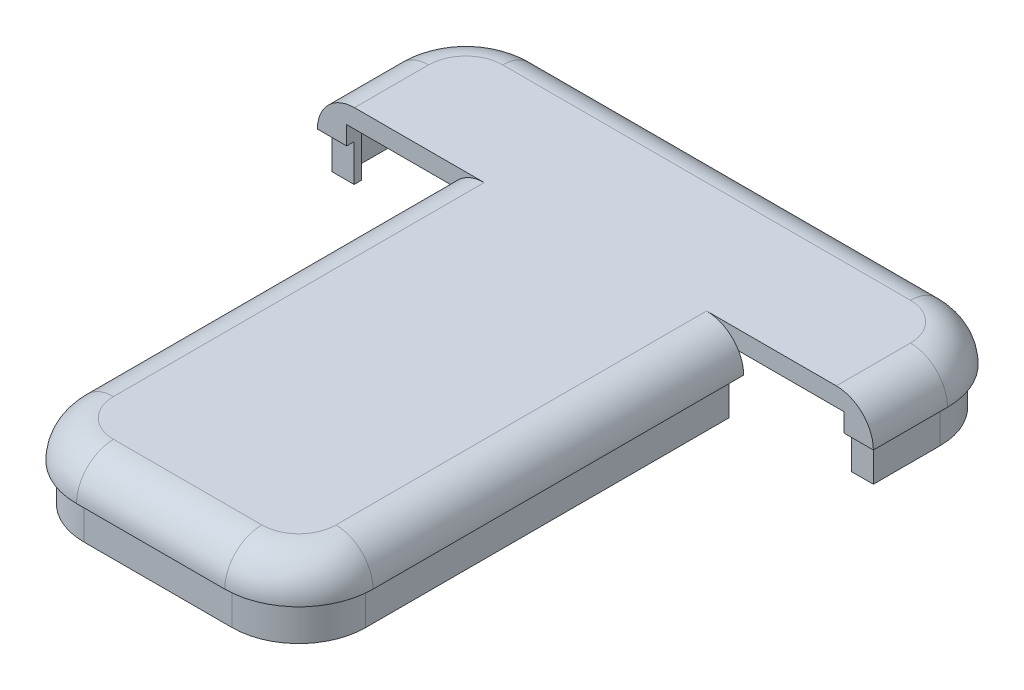
SolidWorks part; units mm, degrees
ref_plane "Front Plane" through (0, 0, 0) normal (0, 0, 1) x (1, 0, 0)
ref_plane "Top Plane" through (0, 0, 0) normal (0, 1, 0) x (1, 0, 0)
ref_plane "Right Plane" through (0, 0, 0) normal (1, 0, 0) x (0, 0, -1)
sketch "Sketch1" plane through (0, 0, 0) normal (0, 1, 0) x (1, 0, 0)
  line L0 (0, 0) -> (0, 152.4)
  line L1 (0, 152.4) -> (-44.45, 152.4)
  line L2 (-44.45, 152.4) -> (-44.45, 203.2)
  line L3 (-44.45, 203.2) -> (146.05, 203.2)
  line L4 (0, 0) -> (101.6, 0)
  line L5 (50.8, 203.2) -> (50.8, 0) construction
  line L6 (101.6, 0) -> (101.6, 152.4)
  line L7 (101.6, 152.4) -> (146.05, 152.4)
  line L8 (146.05, 152.4) -> (146.05, 203.2)
  dimension "D2" = 152.4
  dimension "D3" = 50.8
  dimension "D4" = 44.45
  dimension "D5" = 95.25
extrude "Boss-Extrude1" add sketch "Sketch1" along normal blind 12.7
fillet "Fillet5" radius 25.4 4 edges at (-44.45, 6.35, -203.2) (0, 6.35, 0) (101.6, 6.35, 0) (146.05, 6.35, -203.2)
fillet "Fillet6" radius 12.7 10 edges at (94.1605, 12.7, -7.4395) (50.8, 12.7, 0) (7.4395, 12.7, -7.4395) (0, 12.7, -88.9) (101.6, 12.7, -88.9) (146.05, 12.7, -165.1) (138.6105, 12.7, -195.7605) (-44.45, 12.7, -165.1) (-37.0105, 12.7, -195.7605) (50.8, 12.7, -203.2)
shell "Shell1" thickness 2.54 removed face at (50.8, 0, -118.5333)
ref_plane "Plane2" through (0, 0, 0) normal (0, 1, 0) x (1, 0, 0)
sketch "Sketch3" plane through (0, 0, 0) normal (0, 1, 0) x (1, 0, 0)
  line L16 (96.52, 157.48) -> (140.97, 157.48)
  line L17 (140.97, 157.48) -> (140.97, 177.8)
  line L18 (120.65, 198.12) -> (-19.05, 198.12)
  line L19 (-39.37, 177.8) -> (-39.37, 157.48)
  line L20 (-39.37, 157.48) -> (5.08, 157.48)
  line L21 (5.08, 157.48) -> (5.08, 25.4)
  line L22 (25.4, 5.08) -> (76.2, 5.08)
  line L23 (96.52, 25.4) -> (96.52, 157.48)
  line L24 (96.52, 157.48) -> (140.97, 157.48)
  line L25 (140.97, 157.48) -> (140.97, 177.8)
  line L26 (120.65, 198.12) -> (-19.05, 198.12)
  line L27 (-39.37, 177.8) -> (-39.37, 157.48)
  line L28 (-39.37, 157.48) -> (5.08, 157.48)
  line L29 (5.08, 157.48) -> (5.08, 25.4)
  line L30 (25.4, 5.08) -> (76.2, 5.08)
  line L31 (96.52, 25.4) -> (96.52, 157.48)
  arc A8 (140.97, 177.8) -> (120.65, 198.12) centre (120.65, 177.8) ccw
  arc A9 (-19.05, 198.12) -> (-39.37, 177.8) centre (-19.05, 177.8) ccw
  arc A10 (5.08, 25.4) -> (25.4, 5.08) centre (25.4, 25.4) ccw
  arc A11 (76.2, 5.08) -> (96.52, 25.4) centre (76.2, 25.4) ccw
  arc A12 (140.97, 177.8) -> (120.65, 198.12) centre (120.65, 177.8) ccw
  arc A13 (-19.05, 198.12) -> (-39.37, 177.8) centre (-19.05, 177.8) ccw
  arc A14 (5.08, 25.4) -> (25.4, 5.08) centre (25.4, 25.4) ccw
  arc A15 (76.2, 5.08) -> (96.52, 25.4) centre (76.2, 25.4) ccw
  dimension "D1" = 2.54
extrude "Extrude-Thin1" add sketch "Sketch3" along normal up to next thin thin type one direction wall 2.54
extrude "Extrude-Thin2" add sketch "Sketch3<2>" against normal blind 12.7 thin thin type one direction wall 2.54
sketch "Sketch3<2>" plane through (0, 0, 0) normal (0, 1, 0) x (1, 0, 0) same geometry as "Sketch3"
sketch "Sketch4" plane through (0, 0, 0) normal (0, 1, 0) x (1, 0, 0)
  line L0 (0, 152.4) -> (5.08, 152.4) construction
  line L1 (101.6, 152.4) -> (96.52, 152.4) construction
  line L2 (96.52, 152.4) -> (5.08, 152.4)
extrude "Extrude-Thin3" add sketch "Sketch4" along normal up to next thin thin type one direction reverse wall 2.54
sketch "Sketch5" plane through (0, 0, -149.86) normal (0, 0, 1) x (1, 0, 0)
  line L0 (96.52, 0) -> (5.08, 0) construction
  line L1 (46.99, 0) -> (54.61, 0)
  arc A0 (54.61, 0) -> (46.99, 0) centre (50.8, 0) ccw
extrude "Cut-Extrude1" cut sketch "Sketch5" against normal up to next
sketch "Sketch6" plane through (0, -12.7, 0) normal (0, -1, 0) x (1, 0, 0)
  line L0 (50.8, -5.08) -> (50.8, -200.66) construction
  line L1 (25.4, -5.08) -> (76.2, -5.08) construction
  line L2 (120.65, -200.66) -> (-19.05, -200.66) construction
  line L3 (96.52, -154.94) -> (136.017, -154.94)
  line L4 (99.06, -154.94) -> (143.51, -154.94) construction
  line L7 (96.52, -157.48) -> (96.52, -154.94)
  line L10 (5.08, -154.94) -> (-34.417, -154.94)
  line L11 (5.08, -157.48) -> (5.08, -154.94)
  line L12 (2.54, -154.94) -> (2.54, -149.86)
  line L13 (2.54, -154.94) -> (2.54, -25.4) construction
  line L14 (2.54, -149.86) -> (5.08, -149.86)
  line L15 (5.08, -157.48) -> (5.08, -25.4) construction
  line L16 (5.08, -149.86) -> (5.08, -154.94)
  line L17 (2.54, -154.94) -> (5.08, -154.94)
  line L18 (99.06, -154.94) -> (96.52, -154.94)
  line L19 (99.06, -154.94) -> (99.06, -149.86)
  line L20 (99.06, -149.86) -> (96.52, -149.86)
  line L21 (96.52, -149.86) -> (96.52, -154.94)
  line L22 (96.52, -157.48) -> (136.017, -157.48)
  line L23 (96.52, -157.48) -> (140.97, -157.48) construction
  line L24 (136.017, -157.48) -> (136.017, -154.94)
  line L25 (-34.417, -154.94) -> (-34.417, -157.48)
  line L26 (-39.37, -157.48) -> (5.08, -157.48) construction
  line L27 (-34.417, -157.48) -> (5.08, -157.48)
  line M7 (96.52, -25.4) -> (96.52, -157.48)
  line M8 (96.52, -157.48) -> (140.97, -157.48)
  line M14 (-39.37, -157.48) -> (5.08, -157.48)
  line M15 (5.08, -157.48) -> (5.08, -25.4)
  line M22 (2.54, -25.4) -> (2.54, -154.94)
  line M23 (2.54, -154.94) -> (-41.91, -154.94)
  line M29 (143.51, -154.94) -> (99.06, -154.94)
extrude "Cut-Extrude3" cut sketch "Sketch6" against normal blind 12.7 contours L10 M15 M23 M14 | L14 L10 M22 M15 | L3 M29 M7 M8 | L18 L19 L20 L21 region at (116.2685, -12.7, -156.21) region at (-14.6685, -12.7, -156.21) region at (3.81, -12.7, -152.4)
ref_plane "Plane3" through (0, 0, -152.4) normal (0, 0, 1) x (1, 0, 0)
sketch "Sketch7" plane through (0, 0, -152.4) normal (0, 0, 1) x (1, 0, 0)
  line L0 (-44.45, 0) -> (146.05, 0) construction
  line L1 (50.8, 0) -> (50.8, 30.4507) construction
  line L2 (0, 0) -> (-34.417, 0)
  line L3 (-34.417, 0) -> (-34.417, 6.35)
  line L4 (-34.417, 6.35) -> (0, 6.35)
  line L5 (0, 6.35) -> (0, 0)
  line L6 (136.017, 6.35) -> (101.6, 6.35)
  line L7 (136.017, 0) -> (136.017, 6.35)
  line L8 (101.6, 0) -> (136.017, 0)
  line L9 (101.6, 6.35) -> (101.6, 0)
extrude "Cut-Extrude4" cut sketch "Sketch7" against normal up to next
sketch "Sketch8" plane through (0, 0, 0) normal (0, -1, 0) x (1, 0, 0)
  line L0 (70.5122, -152.4) -> (-70.5122, -152.4) construction
  line L1 (0, -157.48) -> (5.08, -157.48)
  line L2 (0, -157.48) -> (0, -152.4)
  line L3 (0, -152.4) -> (5.08, -152.4)
  line L4 (5.08, -157.48) -> (5.08, -152.4)
  line L5 (5.08, -157.48) -> (5.08, -152.4) construction
  line L7 (96.52, -157.48) -> (101.6, -157.48)
  line L8 (96.52, -157.48) -> (96.52, -152.4)
  line L9 (96.52, -152.4) -> (101.6, -152.4)
  line L10 (101.6, -157.48) -> (101.6, -152.4)
extrude "Cut-Extrude5" cut sketch "Sketch8" against normal blind 6.35
